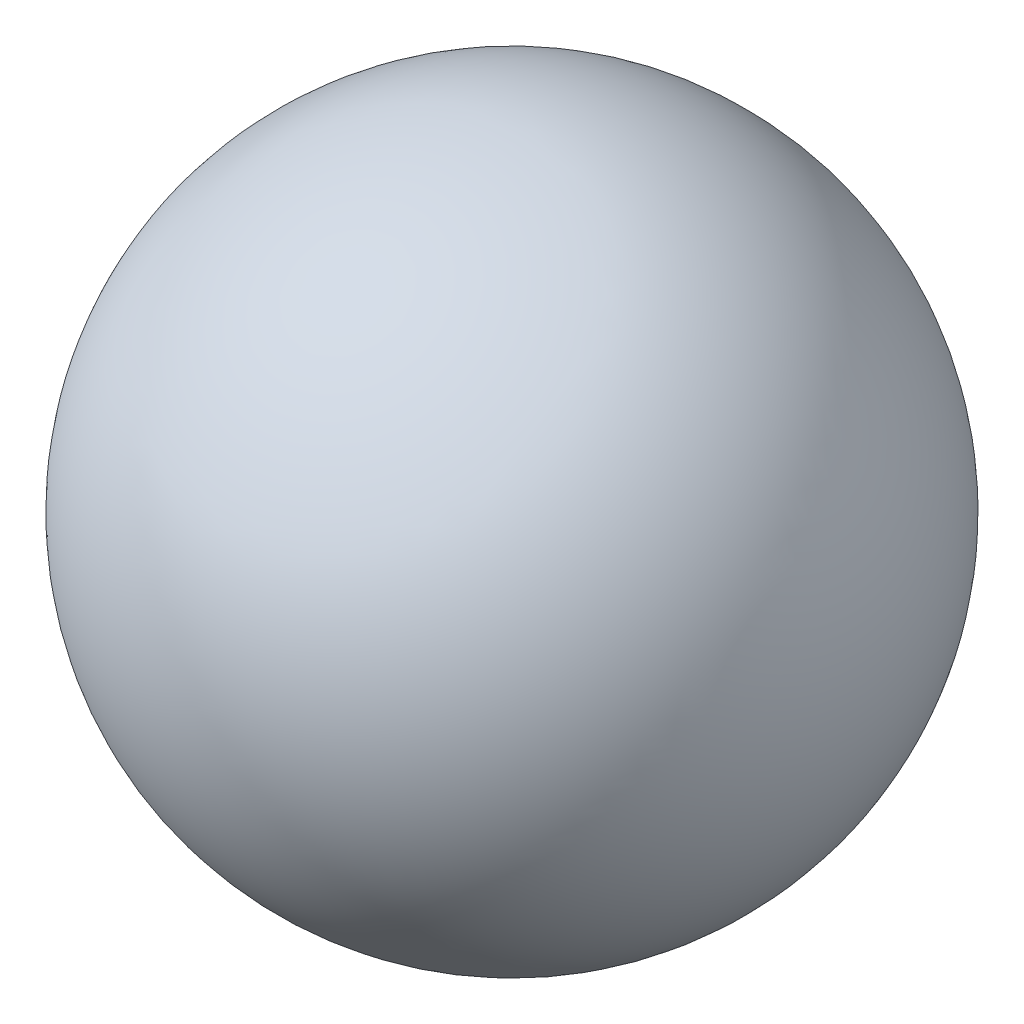
SolidWorks part; units mm, degrees
ref_plane "Plan de face" through (0, 0, 0) normal (0, 0, 1) x (1, 0, 0)
ref_plane "Plan de dessus" through (0, 0, 0) normal (0, 1, 0) x (1, 0, 0)
ref_plane "Plan de droite" through (0, 0, 0) normal (1, 0, 0) x (0, 0, -1)
sketch "Esquisse1" plane through (0, 0, 0) normal (0, 0, 1) x (1, 0, 0)
  line L0 (-1000, 0) -> (49000, 0) construction
  circle A0 centre (0, 0) radius 2.5
  dimension "D1" = 5
revolve "Révolution1" add sketch "Esquisse1" angle 360 about L0 region at (0, 1.061, 0)
